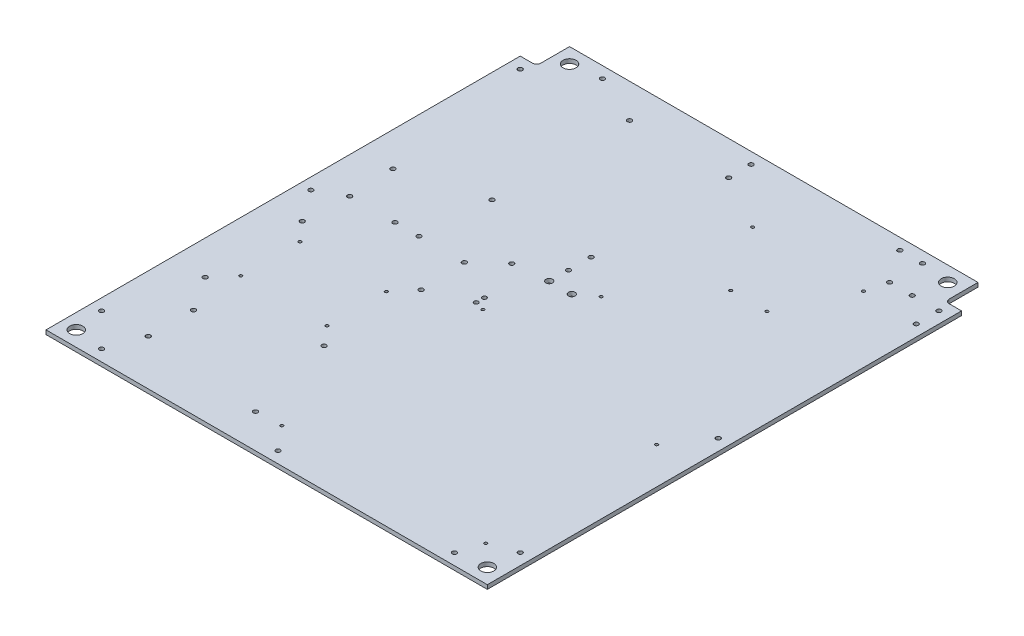
SolidWorks part; units mm, degrees
ref_plane "Front" through (0, 0, 0) normal (0, 0, 1) x (1, 0, 0)
ref_plane "Top" through (0, 0, 0) normal (0, 1, 0) x (1, 0, 0)
ref_plane "Right" through (0, 0, 0) normal (1, 0, 0) x (0, 0, -1)
sketch "Sketch1" plane through (0, 0, 0) normal (0, 1, 0) x (1, 0, 0)
  line L1 (170.434, -195.834) -> (-170.434, -195.834)
  line L2 (170.434, -195.834) -> (170.434, 195.834)
  line L3 (170.434, 195.834) -> (-170.434, 195.834)
  line L4 (-170.434, -195.834) -> (-170.434, 195.834)
  line L5 (170.434, -195.834) -> (-170.434, 195.834) construction
  line L6 (170.434, 195.834) -> (-170.434, -195.834) construction
  point P0 (0, 0)
  dimension "D1" = 340.868
  dimension "D2" = 391.668
extrude "Boss-Extrude1" add sketch "Sketch1" along normal blind 3.175
sketch "Sketch2" plane through (0, 3.175, 0) normal (0, 1, 0) x (1, 0, 0)
  line L0 (170.434, 195.834) -> (-170.434, 195.834) construction
  line L1 (-170.434, 195.834) -> (-157.734, 195.834)
  line L2 (-170.434, 195.834) -> (-170.434, 170.434)
  line L3 (-170.434, 170.434) -> (-160.909, 170.434)
  line L4 (-157.734, 195.834) -> (-157.734, 173.609)
  line L5 (170.434, 195.834) -> (157.734, 195.834)
  line L6 (170.434, 195.834) -> (170.434, 170.434)
  line L7 (170.434, 170.434) -> (160.909, 170.434)
  line L8 (157.734, 195.834) -> (157.734, 173.609)
  arc A0 (-157.734, 173.609) -> (-160.909, 170.434) centre (-160.909, 173.609) cw
  arc A1 (157.734, 173.609) -> (160.909, 170.434) centre (160.909, 173.609) ccw
  dimension "D1" = 3.175
  dimension "D2" = 25.4
  dimension "D3" = 12.7
extrude "Cut-Extrude1" cut sketch "Sketch2" against normal blind 10
hole_wizard "3/8 Clearance Hole1" positions "Sketch3" profile "Sketch4" hole size "3/8" standard "ANSI Inch" end condition through all
sketch "Sketch3" plane through (0, 3.175, 0) normal (0, 1, 0) x (1, 0, 0)
  line L0 (158.75, -184.15) -> (0, -184.15) construction
  line L1 (0, -184.15) -> (-158.75, -184.15) construction
  line L2 (-158.75, -184.15) -> (-158.75, -12.7) construction
  line L3 (-158.75, -12.7) -> (-158.75, 158.75) construction
  line L4 (-158.75, 158.75) -> (158.75, 158.75) construction
  line L5 (158.75, 158.75) -> (158.75, -12.7) construction
  line L6 (158.75, -12.7) -> (158.75, -184.15) construction
  line L8 (146.05, 184.15) -> (0, 184.15) construction
  line L9 (0, 184.15) -> (-146.05, 184.15) construction
  line L10 (-146.05, 184.15) -> (-157.734, 195.834) construction
  line L12 (157.734, 195.834) -> (146.05, 184.15) construction
  line L14 (-158.75, 158.75) -> (-170.434, 170.434) construction
  line L16 (-158.75, -184.15) -> (-170.434, -195.834) construction
  line L18 (158.75, 158.75) -> (170.434, 170.434) construction
  line L20 (158.75, -184.15) -> (170.434, -195.834) construction
  line L21 (158.75, -184.15) -> (158.75, -195.834) construction
  line L22 (-170.434, -195.834) -> (170.434, -195.834) construction
  line L24 (158.75, -184.15) -> (170.434, -184.15) construction
  line L25 (170.434, -195.834) -> (170.434, 170.434) construction
  point P0 (158.75, -184.15)
  point P2 (-158.75, -184.15)
  point P94 (-146.05, 184.15)
  point P96 (146.05, 184.15)
  dimension "D1" = 11.684
sketch "Sketch4" plane through (158.75, 3.175, 184.15) normal (1, 0, 0) x (0, 0, 1)
  line L0 (0, 0) -> (0, 3.175)
  line L1 (0, 3.175) -> (5.0419, 3.175)
  line L2 (5.0419, 3.175) -> (5.0419, 0)
  line L5 (5.0419, 0) -> (0, 0)
  line L11 (0, -6.35) -> (0, 107.95) construction
  dimension "Thru Hole Dia." = 10.0838
  dimension "Thru Hole Depth" = 3.175
hole_wizard "#4-40 Tapped Hole2" positions "Sketch9" profile "Sketch10" tap size "#4-40" standard "ANSI Inch" end condition through all
sketch "Sketch9" plane through (0, 3.175, 0) normal (0, 1, 0) x (1, 0, 0)
  circle A0 centre (33.725, 145.759) radius 1.6319 construction
  circle A1 centre (119.375, 145.759) radius 1.6319 construction
  circle A2 centre (142.14, -168.81) radius 1.95 construction
  circle A3 centre (-131.3281, -38.806) radius 2.7051 construction
  circle A4 centre (-64.6531, -38.806) radius 2.7051 construction
  circle A5 centre (-131.3281, -84.526) radius 2.7051 construction
  circle A6 centre (-64.6531, -84.526) radius 2.7051 construction
  point P4 (119.375, 145.759)
  point P6 (33.725, 145.759)
  point P20 (21.73, 40.754)
  point P23 (67.7, 94.894)
  point P26 (95.6, 94.894)
  point P30 (-15.34, -13.51)
  point P33 (142.14, -36.73)
  point P36 (142.14, -36.73)
  point P39 (-15.34, -168.81)
  point P42 (142.14, -168.81)
  point P48 (-64.6531, -38.806)
  point P50 (-64.6531, -84.526)
  point P52 (-131.3281, -38.806)
  point P54 (-131.3281, -84.526)
cosmetic thread "Hole Thread17" parameters "D2"=2.8448
cosmetic thread "Hole Thread18" parameters "D2"=2.8448
sketch "Sketch10" plane through (119.375, 3.175, -145.759) normal (1, 0, 0) x (0, 0, 1)
  line L0 (0, 0) -> (0, 3.175)
  line L1 (0, 3.175) -> (1.1303, 3.175)
  line L2 (1.1303, 3.175) -> (1.1303, 0)
  line L5 (1.1303, 0) -> (0, 0)
  line L11 (0, -6.35) -> (0, 107.95) construction
  dimension "Thru Tap Drill Dia." = 2.2606
  dimension "Thru Tap Drill Depth" = 3.175
cosmetic thread "Hole Thread19" parameters "D2"=2.8448
cosmetic thread "Hole Thread20" parameters "D2"=2.8448
cosmetic thread "Hole Thread21" parameters "D2"=2.8448
cosmetic thread "Hole Thread22" parameters "D2"=2.8448
cosmetic thread "Hole Thread23" parameters "D2"=2.8448
cosmetic thread "Hole Thread24" parameters "D2"=2.8448
cosmetic thread "Hole Thread25" parameters "D2"=2.8448
cosmetic thread "Hole Thread26" parameters "D2"=2.8448
cosmetic thread "Hole Thread27" parameters "D2"=2.8448
cosmetic thread "Hole Thread28" parameters "D2"=2.8448
cosmetic thread "Hole Thread29" parameters "D2"=2.8448
cosmetic thread "Hole Thread30" parameters "D2"=2.8448
hole_wizard "#8-32 Tapped Hole2" positions "Sketch13" profile "Sketch14" tap size "#8-32" standard "ANSI Inch" end condition through all
sketch "Sketch13" plane through (0, 3.175, 0) normal (0, 1, 0) x (1, 0, 0)
  line L34 (-161.684, 161.684) -> (-161.684, -161.684)
  line L36 (161.684, 144.184) -> (161.684, -161.684)
  line L38 (-123.584, 187.084) -> (106.084, 187.084)
  line L39 (106.084, 187.084) -> (123.584, 187.084)
  line L40 (123.584, 187.084) -> (123.584, 161.684)
  line L42 (123.584, 161.684) -> (141.084, 161.684)
  line L43 (141.084, 161.684) -> (161.684, 161.684)
  line L45 (161.684, 161.684) -> (161.684, 144.184)
  line L47 (-8.584, 187.084) -> (-8.584, 169.584)
  line L48 (-8.584, 169.584) -> (-8.584, 63.334)
  line L50 (-8.584, 63.334) -> (-8.584, 45.834)
  line L51 (-8.584, 45.834) -> (-144.184, 45.834)
  line L52 (-144.184, 45.834) -> (-161.684, 45.834)
  line L54 (-34.884, 45.834) -> (-34.884, 28.334)
  line L55 (-34.884, 28.334) -> (-34.884, -169.584)
  line L56 (-34.884, -169.584) -> (-34.884, -187.084)
  line L58 (-136.284, -187.084) -> (136.284, -187.084)
  line L60 (-161.684, -24.166) -> (-144.184, -24.166)
  line L61 (-144.184, -24.166) -> (-52.384, -24.166)
  line L62 (-52.384, -24.166) -> (-34.884, -24.166)
  line L64 (-161.684, -99.166) -> (-144.184, -99.166)
  line L65 (-144.184, -99.166) -> (-52.384, -99.166)
  line L66 (-52.384, -99.166) -> (-34.884, -99.166)
  line L68 (-161.684, 10.834) -> (-142.534, 10.834)
  line L69 (-142.534, 10.834) -> (-107.534, 10.834)
  line L70 (-107.534, 10.834) -> (-89.034, 10.834)
  line L71 (-89.034, 10.834) -> (-54.034, 10.834)
  line L72 (-54.034, 10.834) -> (-34.884, 10.834)
  line L74 (-85.134, 45.834) -> (-85.134, 63.334)
  line L75 (-85.134, 63.334) -> (-85.134, 169.584)
  line L76 (-85.134, 169.584) -> (-85.134, 187.084)
  line L78 (-170.434, 170.434) -> (-170.434, -195.834) construction
  line L79 (157.734, 195.834) -> (-157.734, 195.834) construction
  line L81 (170.434, -195.834) -> (170.434, 170.434) construction
  line L82 (-170.434, -195.834) -> (170.434, -195.834) construction
  line L83 (-170.434, 170.434) -> (-160.909, 170.434) construction
  line L84 (160.909, 170.434) -> (170.434, 170.434) construction
  line L85 (157.734, 195.834) -> (157.734, 173.609) construction
  line L86 (-157.734, 173.609) -> (-157.734, 195.834) construction
  line L87 (-76.384, 45.834) -> (-76.384, 10.834) construction
  line L88 (-76.384, 10.834) -> (-76.384, -24.166) construction
  line L90 (-161.684, 63.334) -> (-85.134, 63.334) construction
  line L92 (-85.134, 63.334) -> (-8.584, 63.334) construction
  line L93 (-126.684, -99.166) -> (-126.684, -125.625)
  line L94 (-126.684, -125.625) -> (-126.684, -160.625)
  line L95 (-126.684, -160.625) -> (-126.684, -187.084)
  point P146 (-161.684, -161.684)
  point P148 (-161.684, 0)
  point P150 (-161.684, 161.684)
  point P152 (-144.184, 45.834)
  point P154 (-8.584, 45.834)
  point P156 (-144.184, -24.166)
  point P158 (-52.384, -24.166)
  point P160 (-144.184, -99.166)
  point P162 (-52.384, -99.166)
  point P164 (-34.884, 28.334)
  point P166 (-34.884, -169.584)
  point P168 (-136.284, -187.084)
  point P170 (0, -187.084)
  point P172 (136.284, -187.084)
  point P174 (161.684, -161.684)
  point P176 (161.684, -8.75)
  point P178 (161.684, 144.184)
  point P180 (141.084, 161.684)
  point P182 (161.684, 161.684)
  point P184 (123.584, 161.684)
  point P186 (123.584, 187.084)
  point P188 (106.084, 187.084)
  point P190 (-123.584, 187.084)
  point P192 (-8.75, 187.084)
  point P194 (-8.584, 169.584)
  point P196 (-8.584, 63.334)
  point P198 (-142.534, 10.834)
  point P200 (-107.534, 10.834)
  point P202 (-89.034, 10.834)
  point P204 (-54.034, 10.834)
  point P206 (-85.134, 63.334)
  point P208 (-85.134, 169.584)
  point P345 (-126.684, -125.625)
  point P347 (-126.684, -160.625)
  dimension "D1" = 8.75
  dimension "D2" = 8.75
  dimension "D3" = 8.75
  dimension "D4" = 8.75
  dimension "D5" = 34.15
  dimension "D6" = 8.75
  dimension "D7" = 8.75
  dimension "D8" = 17.5
  dimension "D9" = 34.15
  dimension "D10" = 17.5
  dimension "D11" = 17.5
  dimension "D12" = 34.15
  dimension "D13" = 34.15
  dimension "D14" = 34.15
  dimension "D15" = 34.15
  dimension "D16" = 17.5
  dimension "D17" = 17.5
  dimension "D18" = 17.5
  dimension "D19" = 17.5
  dimension "D20" = 17.5
  dimension "D21" = 17.5
  dimension "D22" = 17.5
  dimension "D23" = 17.5
  dimension "D24" = 150
  dimension "D25" = 161.85
  dimension "D26" = 135.55
  dimension "D27" = 70
  dimension "D28" = 75
  dimension "D29" = 35
  dimension "D30" = 35
  dimension "D31" = 53.5
  dimension "D32" = 35
  dimension "D33" = 35
sketch "Sketch14" plane through (-161.684, 3.175, 161.684) normal (1, 0, 0) x (0, 0, 1)
  line L0 (0, 0) -> (0, 3.175)
  line L1 (0, 3.175) -> (1.7272, 3.175)
  line L2 (1.7272, 3.175) -> (1.7272, 0)
  line L5 (1.7272, 0) -> (0, 0)
  line L11 (0, -6.35) -> (0, 107.95) construction
  dimension "Thread Major Dia." = 3.4544
  dimension "Thru Tap Drill Depth" = 3.175
hole_wizard "#4 Clearance Hole1" positions "Sketch15" profile "Sketch16" hole size "#4" standard "ANSI Inch"
sketch "Sketch15" plane through (0, 3.175, 0) normal (0, 1, 0) x (1, 0, 0)
  point P0 (-22.642, -11.3606)
  point P3 (-22.642, -5.0106)
sketch "Sketch16" plane through (-22.642, 3.175, 11.3606) normal (1, 0, 0) x (0, 0, 1)
  line L0 (0, 0) -> (0, 8.9906)
  line L1 (0, 8.9906) -> (1.6319, 8.01)
  line L2 (1.6319, 8.01) -> (1.6319, 0)
  line L5 (1.6319, 0) -> (0, 0)
  line L10 (0, 8.9906) -> (-1.632, 8.01) construction
  line L11 (0, -6.35) -> (0, 107.95) construction
  dimension "Hole Dia." = 3.2639
  dimension "Hole Depth" = 8.01
  dimension "Drill Angle" = 118
hole_wizard "#10 Clearance Hole1" positions "Sketch17" profile "Sketch18" hole size "#10" standard "ANSI Inch" end condition through all
sketch "Sketch17" plane through (0, 0, 0) normal (0, -1, 0) x (-1, 0, 0)
  circle A0 centre (-8.7376, 31.1216) radius 2.032 construction
  circle A1 centre (8.7376, 31.1216) radius 2.032 construction
  point P0 (8.7376, 31.1216)
  point P2 (-8.7376, 31.1216)
sketch "Sketch18" plane through (-8.7376, 0, -31.1216) normal (1, 0, 0) x (0, 0, -1)
  line L0 (0, 0) -> (0, 3.175)
  line L1 (0, 3.175) -> (2.5527, 3.175)
  line L2 (2.5527, 3.175) -> (2.5527, 0)
  line L5 (2.5527, 0) -> (0, 0)
  line L11 (0, -6.35) -> (0, 107.95) construction
  dimension "Thru Hole Dia." = 5.1054
  dimension "Thru Hole Depth" = 3.175
